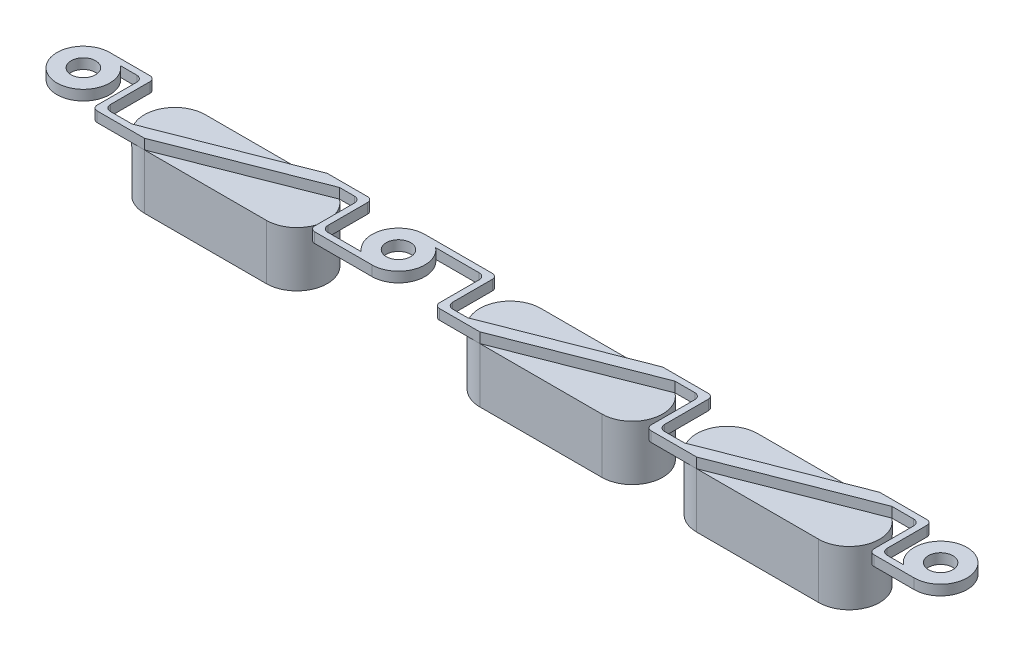
SolidWorks part; units mm, degrees
ref_plane "前视基准面" through (0, 0, 0) normal (0, 0, 1) x (1, 0, 0)
ref_plane "上视基准面" through (0, 0, 0) normal (0, 1, 0) x (1, 0, 0)
ref_plane "右视基准面" through (0, 0, 0) normal (1, 0, 0) x (0, 0, -1)
sketch "草图1" plane through (0, 0, 0) normal (0, 1, 0) x (1, 0, 0)
  line L0 (-3, 0) -> (3, 0) construction
  line L1 (-3, 1.5) -> (3, 1.5)
  line L2 (-3, -1.5) -> (3, -1.5)
  line L3 (-19.5, 0) -> (-13.5, 0) construction
  line L4 (-19.5, 1.5) -> (-13.5, 1.5)
  line L5 (-19.5, -1.5) -> (-13.5, -1.5)
  line L6 (7.67, 0) -> (13.67, 0) construction
  line L7 (7.67, 1.5) -> (13.67, 1.5)
  line L8 (7.67, -1.5) -> (13.67, -1.5)
  arc A0 (-3, 1.5) -> (-3, -1.5) centre (-3, 0) ccw
  arc A1 (3, -1.5) -> (3, 1.5) centre (3, 0) ccw
  arc A2 (-19.5, 1.5) -> (-19.5, -1.5) centre (-19.5, 0) ccw
  arc A3 (-13.5, -1.5) -> (-13.5, 1.5) centre (-13.5, 0) ccw
  arc A4 (7.67, 1.5) -> (7.67, -1.5) centre (7.67, 0) ccw
  arc A5 (13.67, -1.5) -> (13.67, 1.5) centre (13.67, 0) ccw
  circle A6 centre (18.17, 0) radius 1.5 construction
  circle A7 centre (-8.5, 0) radius 1.5 construction
  circle A8 centre (-24, 0) radius 1.5 construction
  point P2 (0, 0)
  point P10 (-16.5, 0)
  point P17 (10.67, 0)
  point P31 (-21, 0)
  point P32 (15.17, 0)
  point P33 (-4.5, 0)
  dimension "D2" = 1.5
  dimension "D5" = 3
  dimension "D1" = 6
  dimension "D3" = 16.5
  dimension "D4" = 10.67
  dimension "D6" = 3
  dimension "D7" = 4
extrude "凸台-拉伸1" add sketch "草图1" along normal blind 2.7 contours L8 A5 L7 A4 | L4 A3 L5 A2 | L1 A1 L2 A0 region at (10.67, 0, 0)
sketch "草图2" plane through (0, 2.7, 0) normal (0, 1, 0) x (1, 0, 0)
  line L0 (-24, 1.3) -> (-22.02, 1.3)
  line L1 (-21.77, 1.05) -> (-21.77, -0.9)
  line L2 (-21.47, -1.2) -> (-20.4, -1.2)
  line L3 (-23.1693, 1) -> (-22.37, 1)
  line L4 (-22.07, 0.7) -> (-22.07, -1.25)
  line L5 (-19.5, -1.5) -> (-21.82, -1.5)
  line L6 (-11.27, -0.7) -> (-11.27, 1.25)
  line L8 (18.17, -1.3) -> (16.19, -1.3)
  line L9 (16.24, 1.25) -> (16.24, -0.7)
  line L10 (13.67, 1.5) -> (15.99, 1.5)
  line L11 (15.94, 0.9) -> (15.94, -1.05)
  line L12 (16.54, -1) -> (17.3393, -1)
  line L13 (-13.5, 1.5) -> (-11.52, 1.5)
  line L14 (-9.3307, -1) -> (-10.97, -1)
  line L15 (-8.5, -1.3) -> (-11.32, -1.3)
  line L16 (-11.87, 1.2) -> (-12.6, 1.2)
  line L17 (-11.57, -1.05) -> (-11.57, 0.9)
  line L18 (-20.4, -1.2) -> (-13.5, 1.5)
  line L19 (-12.6, 1.2) -> (-19.5, -1.5)
  line L20 (-8.5, 1.3) -> (-5.18, 1.3)
  line L21 (-4.63, -1.2) -> (-3.9, -1.2)
  line L22 (-4.93, 1.05) -> (-4.93, -0.9)
  line L23 (-3, -1.5) -> (-4.98, -1.5)
  line L24 (-5.23, 0.7) -> (-5.23, -1.25)
  line L25 (-7.6693, 1) -> (-5.53, 1)
  line L26 (5.49, 1.25) -> (5.49, -0.9)
  line L27 (3.9, 1.2) -> (4.88, 1.2)
  line L28 (7.67, -1.5) -> (5.43, -1.5)
  line L29 (3, 1.5) -> (5.24, 1.5)
  line L30 (5.18, 0.9) -> (5.18, -1.25)
  line L31 (5.79, -1.2) -> (6.77, -1.2)
  line L32 (-3.9, -1.2) -> (3, 1.5)
  line L33 (-3, -1.5) -> (3.9, 1.2)
  line L34 (14.57, 1.2) -> (15.64, 1.2)
  line L35 (7.67, -1.5) -> (14.57, 1.2)
  line L36 (6.77, -1.2) -> (13.67, 1.5)
  arc A0 (-24, 1.3) -> (-23.1693, 1) centre (-24, 0) ccw
  arc A1 (-8.5, -1.3) -> (-7.6693, 1) centre (-8.5, 0) ccw
  arc A3 (-22.02, 1.3) -> (-21.77, 1.05) centre (-22.02, 1.05) cw
  arc A4 (-21.77, -0.9) -> (-21.47, -1.2) centre (-21.47, -0.9) ccw
  arc A5 (-19.5, 1.5) -> (-19.5, -1.5) centre (-19.5, 0) ccw construction
  arc A6 (-22.37, 1) -> (-22.07, 0.7) centre (-22.37, 0.7) cw
  arc A7 (-22.07, -1.25) -> (-21.82, -1.5) centre (-21.82, -1.25) ccw
  arc A8 (18.17, -1.3) -> (17.3393, -1) centre (18.17, 0) ccw
  arc A9 (15.64, 1.2) -> (15.94, 0.9) centre (15.64, 0.9) cw
  arc A10 (15.99, 1.5) -> (16.24, 1.25) centre (15.99, 1.25) cw
  arc A11 (16.24, -0.7) -> (16.54, -1) centre (16.54, -0.7) ccw
  arc A12 (-11.27, 1.25) -> (-11.52, 1.5) centre (-11.52, 1.25) ccw
  arc A13 (15.94, -1.05) -> (16.19, -1.3) centre (16.19, -1.05) ccw
  arc A14 (-11.32, -1.3) -> (-11.57, -1.05) centre (-11.32, -1.05) cw
  arc A15 (-11.57, 0.9) -> (-11.87, 1.2) centre (-11.87, 0.9) ccw
  arc A16 (-10.97, -1) -> (-11.27, -0.7) centre (-10.97, -0.7) cw
  arc A17 (-13.5, -1.5) -> (-13.5, 1.5) centre (-13.5, 0) ccw construction
  circle A18 centre (-24, 0) radius 0.6
  circle A19 centre (-8.5, 0) radius 0.6
  circle A20 centre (18.17, 0) radius 0.6
  arc A21 (-5.18, 1.3) -> (-4.93, 1.05) centre (-5.18, 1.05) cw
  arc A22 (-5.53, 1) -> (-5.23, 0.7) centre (-5.53, 0.7) cw
  arc A23 (-5.23, -1.25) -> (-4.98, -1.5) centre (-4.98, -1.25) ccw
  arc A24 (-4.93, -0.9) -> (-4.63, -1.2) centre (-4.63, -0.9) ccw
  arc A25 (-3, 1.5) -> (-3, -1.5) centre (-3, 0) ccw construction
  arc A26 (-8.5, 1.3) -> (-9.3307, -1) centre (-8.5, 0) ccw
  arc A27 (5.49, -0.9) -> (5.79, -1.2) centre (5.79, -0.9) ccw
  arc A28 (5.18, -1.25) -> (5.43, -1.5) centre (5.43, -1.25) ccw
  arc A29 (4.88, 1.2) -> (5.18, 0.9) centre (4.88, 0.9) cw
  arc A30 (5.24, 1.5) -> (5.49, 1.25) centre (5.24, 1.25) cw
  arc A31 (7.67, 1.5) -> (7.67, -1.5) centre (7.67, 0) ccw construction
  arc A32 (13.67, -1.5) -> (13.67, 1.5) centre (13.67, 0) ccw construction
  arc A34 (3, -1.5) -> (3, 1.5) centre (3, 0) ccw construction
  point P71 (-11.57, -0.075)
  dimension "D1" = 0.3
  dimension "D4" = 0.3
  dimension "D7" = 1.93
  dimension "D13" = 0.3
  dimension "D18" = 2.18
  dimension "D6" = 0.3
  dimension "D2" = 0.3
  dimension "D3" = 0.3
  dimension "D5" = 0.3
  dimension "D8" = 1.93
  dimension "D9" = 0.3
  dimension "D10" = 0.3
  dimension "D11" = 0.3
  dimension "D12" = 1.93
  dimension "D14" = 0.3
  dimension "D15" = 0.3
  dimension "D16" = 1.93
  dimension "D17" = 0.3
  dimension "D19" = 0.3
  dimension "D20" = 2.18
extrude "凸台-拉伸2" add sketch "草图2" along normal blind 0.5 contours A0 L3 A6 L4 A7 L5 L19 L16 A15 L17 A14 L15 A1 L25 A22 L24 A23 L23 L33 L27 A29 L30 A28 L28 L35 L34 A9 L11 A13 L8 A8 L12 A11 L9 A10 L10 L36 L31 A27 L26 A30 L29 L32 L21 A24 L22 A21 L20 A26 L14 A16 L6 A12 L13 L18 L2 A4 L1 A3 L0
extrude "切除-拉伸1" cut sketch "草图2<3>" along normal up to next contours A18 | A19 | A20
sketch "草图2<3>" plane through (0, 2.7, 0) normal (0, 1, 0) x (1, 0, 0) same geometry as "草图2"
